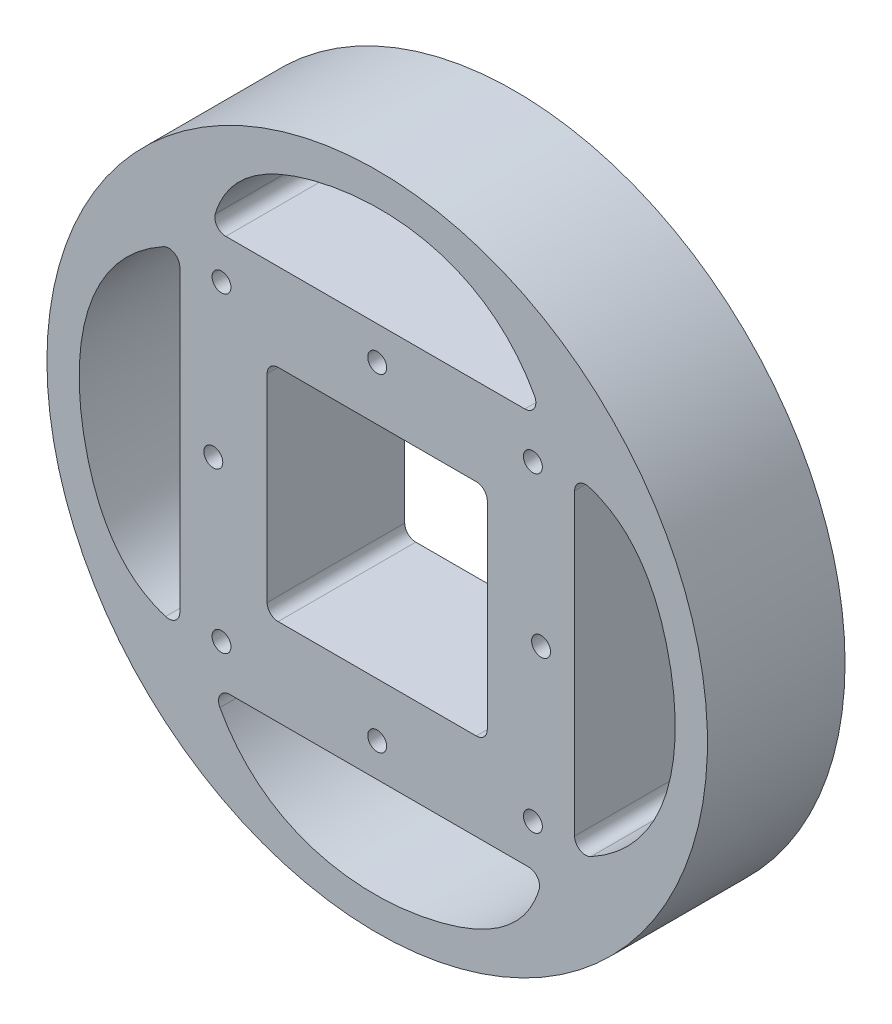
SolidWorks part; units mm, degrees
note: The reader was unsure of these and kept them because the rebuilt part matched: shared geometry of "Sketch4<3>".
material "6061 Alloy"
ref_plane "Front Plane" through (0, 0, 0) normal (0, 0, 1) x (1, 0, 0)
ref_plane "Top Plane" through (0, 0, 0) normal (0, 1, 0) x (1, 0, 0)
ref_plane "Right Plane" through (0, 0, 0) normal (1, 0, 0) x (0, 0, -1)
sketch "Sketch1" plane through (0, 0, 0) normal (0, 0, 1) x (1, 0, 0)
  circle A0 centre (0, 0) radius 76.2
  circle A1 centre (0, 0) radius 69.85
  dimension "D1" = 152.4
  dimension "D2" = 139.7
extrude "Boss-Extrude1" add sketch "Sketch1" along normal blind 107.95
sketch "Sketch3" plane through (0, 0, 0) normal (0, 0, 1) x (1, 0, 0)
  circle A0 centre (0, 0) radius 76.2
extrude "Boss-Extrude2" add sketch "Sketch3" along normal blind 6.35 and the other way blind 31.75
sketch "Sketch4" plane through (0, 0, 6.35) normal (0, 0, 1) x (1, 0, 0)
  line L1 (-19.05, 19.05) -> (19.05, 19.05)
  line L2 (-19.05, 19.05) -> (-19.05, -19.05)
  line L3 (-19.05, -19.05) -> (19.05, -19.05)
  line L4 (19.05, 19.05) -> (19.05, -19.05)
  point P5 (0, 19.05)
  point P7 (-19.05, 0)
  dimension "D1" = 38.1
  dimension "2.5" = 38.1
extrude "Cut-Extrude1" [suppressed] cut sketch "Sketch4" against normal blind 1.27
sketch "Sketch5" plane through (0, 0, 6.35) normal (0, 0, 1) x (1, 0, 0)
  line L5 (-25.4, -25.4) -> (25.4, -25.4) construction
  line L6 (-25.4, -25.4) -> (-25.4, 25.4) construction
  line L7 (-25.4, 25.4) -> (25.4, 25.4) construction
  line L8 (25.4, -25.4) -> (25.4, 25.4) construction
  circle A0 centre (0, 37.813) radius 2.1828
  circle A1 centre (37.813, 0) radius 2.1828
  circle A2 centre (-37.813, 0) radius 2.1828
  circle A3 centre (0, -37.813) radius 2.1828
  point P20 (0, -25.4)
  point P21 (25.4, 0)
  dimension "D1" = 4.3656
  dimension "D2" = 4.3656
  dimension "D3" = 4.3656
  dimension "D4" = 4.3656
  dimension "D5" = 12.413
  dimension "D6" = 12.413
  dimension "D7" = 12.413
  dimension "D8" = 12.413
  dimension "D9" = 50.8
  dimension "D10" = 50.8
extrude "Cut-Extrude2" cut sketch "Sketch5" against normal through all contours L6 L5 L8 L7 | A1 | A0 | A2 | A3
sketch "Sketch10" plane through (0, 0, 107.95) normal (0, 0, 1) x (1, 0, 0)
  line L1 (68.5113, -13.6099) -> (73.6429, -1.5885)
  line L2 (73.6429, -1.5885) -> (69.0344, 10.6431)
  line L3 (69.0344, 10.6431) -> (69.745, 23.6947)
  line L4 (69.745, 23.6947) -> (61.231, 33.6124)
  line L5 (61.231, 33.6124) -> (57.4348, 46.1199)
  line L6 (57.4348, 46.1199) -> (46.0422, 52.5275)
  line L7 (46.0422, 52.5275) -> (38.1971, 62.9824)
  line L8 (38.1971, 62.9824) -> (25.3, 65.1071)
  line L9 (25.3, 65.1071) -> (14.3523, 72.2482)
  line L10 (14.3523, 72.2482) -> (1.5063, 69.8338)
  line L11 (1.5063, 69.8338) -> (-11.2236, 72.7999)
  line L12 (-11.2236, 72.7999) -> (-22.4691, 66.1375)
  line L16 (-22.4691, 66.1375) -> (-35.4458, 64.5708)
  line L17 (-35.4458, 64.5708) -> (-43.7344, 54.464)
  line L18 (-43.7344, 54.464) -> (-55.3927, 48.5536)
  line L19 (-55.3927, 48.5536) -> (-59.7247, 36.2214)
  line L20 (-59.7247, 36.2214) -> (-68.6584, 26.68)
  line L21 (-68.6584, 26.68) -> (-68.5113, 13.6099)
  line L22 (-68.5113, 13.6099) -> (-73.6429, 1.5885)
  line L23 (-73.6429, 1.5885) -> (-69.0344, -10.6431)
  line L24 (-69.0344, -10.6431) -> (-69.745, -23.6947)
  line L25 (-69.745, -23.6947) -> (-69.0344, -10.6431)
  line L26 (-69.0344, -10.6431) -> (-69.745, -23.6947)
  line L27 (-69.745, -23.6947) -> (-61.231, -33.6124)
  line L28 (-61.231, -33.6124) -> (-57.4348, -46.1199)
  line L29 (-57.4348, -46.1199) -> (-46.0422, -52.5275)
  line L30 (-46.0422, -52.5275) -> (-38.1971, -62.9824)
  line L31 (-38.1971, -62.9824) -> (-25.3, -65.1071)
  line L32 (-25.3, -65.1071) -> (-14.3523, -72.2482)
  line L33 (-14.3523, -72.2482) -> (-1.5063, -69.8338)
  line L34 (-1.5063, -69.8338) -> (11.2236, -72.7999)
  line L35 (11.2236, -72.7999) -> (22.4691, -66.1375)
  line L36 (22.4691, -66.1375) -> (35.4458, -64.5708)
  line L37 (35.4458, -64.5708) -> (43.7344, -54.464)
  line L38 (43.7344, -54.464) -> (55.3927, -48.5536)
  line L39 (55.3927, -48.5536) -> (59.7247, -36.2214)
  line L40 (59.7247, -36.2214) -> (68.6584, -26.68)
  line L41 (68.6584, -26.68) -> (68.5113, -13.6099)
  circle A7 centre (0, 0) radius 73.66 construction
  circle A8 centre (0, 0) radius 69.85 construction
  circle A9 centre (0, 0) radius 69.85 construction
  circle M41 centre (0, 0) radius 69.85
  dimension "D1" = 147.32
extrude "Cut-Extrude10" [suppressed] cut sketch "Sketch10" against normal up to surface (69.85 mm away) contours M41 | L20 L21 M41 | L18 L19 M41 | L16 L17 M41 | L11 L12 M41 | L9 L10 M41 | L7 L8 M41 | L5 L6 M41 | L3 L4 M41 | L1 L2 M41 | L40 L41 M41 | L38 L39 M41 | L36 L37 M41 | L34 L35 M41 | L32 L33 M41 | L30 L31 M41 | L28 L29 M41 | L24 L27 M41 | L22 L23 M41
fillet "Fillet1" [suppressed] radius 9.525
sketch "Sketch11" plane through (0, 0, 6.35) normal (0, 0, 1) x (1, 0, 0)
  line L0 (-71.842, 0) -> (0, 71.842) construction
  line L1 (0, 71.842) -> (71.842, 0) construction
  line L2 (71.842, 0) -> (0, -71.842) construction
  line L3 (0, -71.842) -> (-71.842, 0) construction
  line L4 (0, -37.813) -> (37.813, 0) construction
  circle A0 centre (-35.921, 35.921) radius 2.1828
  circle A1 centre (-35.921, -35.921) radius 2.1828
  circle A2 centre (35.921, -35.921) radius 2.1828
  circle A3 centre (35.921, 35.921) radius 2.1828
  dimension "D5" = 90
  dimension "D6" = 4.3656
  dimension "D7" = 4.3656
  dimension "D8" = 4.3656
  dimension "D9" = 4.3656
  dimension "D1" = 101.6
  dimension "D2" = 101.6
  dimension "D3" = 50.8
  dimension "D4" = 50.8
extrude "Cut-Extrude11" cut sketch "Sketch11" against normal through all
extrude "Boss-Extrude3" add sketch "Sketch4<3>" along normal blind 19.05
sketch "Sketch4<3>" plane through (0, 0, 6.35) normal (0, 0, 1) x (1, 0, 0) same geometry as "Sketch4"
sketch "Sketch12" plane through (0, 0, -31.75) normal (0, 0, -1) x (-1, 0, 0)
  circle A0 centre (0, 37.813) radius 4.445
  circle A1 centre (35.921, 35.921) radius 4.445
  circle A2 centre (37.813, 0) radius 4.445
  circle A3 centre (35.921, -35.921) radius 4.445
  circle A4 centre (0, -37.813) radius 4.445
  circle A5 centre (-35.921, -35.921) radius 4.445
  circle A6 centre (-37.813, 0) radius 4.445
  circle A7 centre (-35.921, 35.921) radius 4.445
  circle A8 centre (0, 0) radius 69.85
  dimension "D1" = 8.89
  dimension "D2" = 8.89
  dimension "D3" = 8.89
  dimension "D4" = 8.89
  dimension "D5" = 8.89
  dimension "D6" = 8.89
  dimension "D7" = 8.89
  dimension "D8" = 8.89
extrude "Cut-Extrude12" cut sketch "Sketch12" against normal blind 25.4 from offset 31.75 contours A8 offset against normal yes
sketch "Sketch13" plane through (0, 0, 0) normal (0, 0, -1) x (-1, 0, 0)
  circle A0 centre (0, 0) radius 76.2
extrude "Cut-Extrude13" cut sketch "Sketch13" against normal through all
sketch "Sketch14" plane through (0, 0, 0) normal (0, 0, 1) x (1, 0, 0)
  line L1 (-25.4, 25.4) -> (25.4, 25.4)
  line L2 (-25.4, 25.4) -> (-25.4, -25.4)
  line L3 (-25.4, -25.4) -> (25.4, -25.4)
  line L4 (25.4, 25.4) -> (25.4, -25.4)
  dimension "D1" = 50.8
  dimension "D2" = 50.8
  dimension "D3" = 25.4
  dimension "D4" = 25.4
extrude "Cut-Extrude14" cut sketch "Sketch14" against normal through all
sketch "Sketch15" plane through (0, 0, 0) normal (0, 0, 1) x (1, 0, 0)
  line L0 (-38.1, -45.5403) -> (38.1, -45.5403)
  line L1 (-45.5403, 38.1) -> (-45.5403, -38.1)
  line L2 (38.1, 45.5403) -> (-38.1, 45.5403)
  line L3 (45.5403, -38.1) -> (45.5403, 38.1)
  spline S0 degree 3 poles (-38.1, -45.5403) (-29.0212, -67.0386) (5.8398, -74.5372) (36.0704, -58.5897) (38.1, -45.5403) knots 0 0 0 0 0.631804 1 1 1 1
  spline S1 degree 3 poles (-45.5403, 38.1) (-67.0386, 29.0212) (-74.5372, -5.8398) (-58.5897, -36.0704) (-45.5403, -38.1) knots 0 0 0 0 0.631804 1 1 1 1
  spline S2 degree 3 poles (38.1, 45.5403) (29.0212, 67.0386) (-5.8398, 74.5372) (-36.0704, 58.5897) (-38.1, 45.5403) knots 0 0 0 0 0.631804 1 1 1 1
  spline S3 degree 3 poles (45.5403, -38.1) (67.0386, -29.0212) (74.5372, 5.8398) (58.5897, 36.0704) (45.5403, 38.1) knots 0 0 0 0 0.631804 1 1 1 1
  point P1 (0, -45.5403)
  point P25 (0, 0)
  dimension "D1" = 76.2
  dimension "D2" = 4
extrude "Cut-Extrude15" cut sketch "Sketch15" against normal through all
fillet "Fillet2" radius 2.54 12 edges at (45.5403, 38.1, -15.875) (45.5403, -38.1, -15.875) (38.1, 45.5403, -15.875) (-38.1, 45.5403, -15.875) (25.4, 25.4, -15.875) (25.4, -25.4, -15.875) (-25.4, -25.4, -15.875) (-25.4, 25.4, -15.875) (-45.5403, 38.1, -15.875) (-45.5403, -38.1, -15.875) (-38.1, -45.5403, -15.875) (38.1, -45.5403, -15.875)
